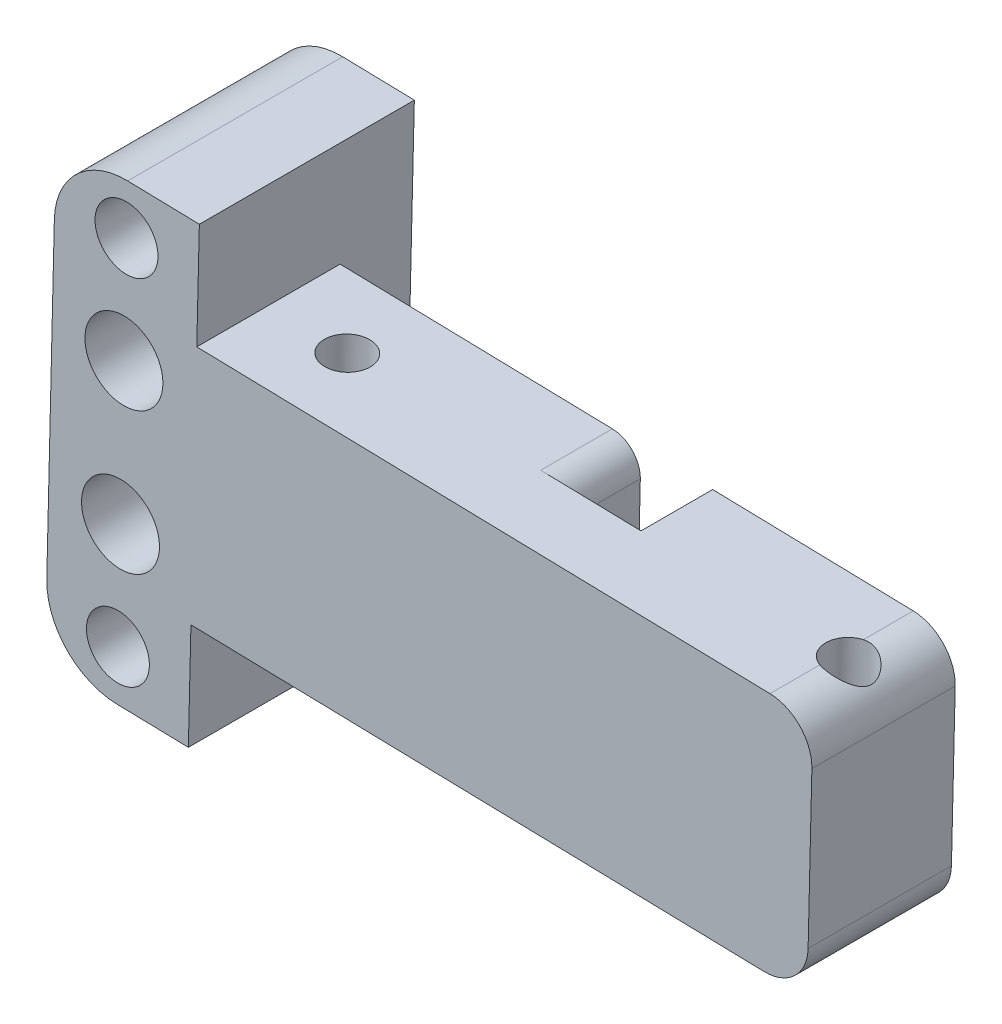
SolidWorks part; units mm, degrees
material "聚丁二烯(PB)"
ref_plane "前视基准面" through (0, 0, 0) normal (0, 0, 1) x (1, 0, 0)
ref_plane "上视基准面" through (0, 0, 0) normal (0, 1, 0) x (1, 0, 0)
ref_plane "右视基准面" through (0, 0, 0) normal (1, 0, 0) x (0, 0, -1)
other "Configuration Table"
sketch "草图1" plane through (0, 0, 0) normal (0, 0, 1) x (1, 0, 0)
  line L0 (24.1852, -7.0163) -> (24.4965, 5.98)
  line L1 (22.545, 8.0273) -> (-13.4447, 8.8895)
  line L2 (-13.4447, 8.8895) -> (-13.2651, 16.3873)
  line L3 (-13.2651, 16.3873) -> (-18.2636, 16.5071)
  line L4 (-23.3819, 11.6283) -> (-23.9088, -10.3654)
  line L5 (-19.03, -15.4837) -> (-14.0315, -15.6035)
  line L6 (-14.0315, -15.6035) -> (-13.8518, -8.1056)
  line L7 (-13.8518, -8.1056) -> (22.1378, -8.9678)
  arc A0 (24.4965, 5.98) -> (22.545, 8.0273) centre (22.4971, 6.0279) ccw
  arc A1 (-18.2636, 16.5071) -> (-23.3819, 11.6283) centre (-18.3834, 11.5085) ccw
  arc A2 (-23.9088, -10.3654) -> (-19.03, -15.4837) centre (-18.9103, -10.4852) ccw
  arc A3 (22.1378, -8.9678) -> (24.1852, -7.0163) centre (22.1857, -6.9684) ccw
  arc A4 (-16.7504, -12.0373) -> (-21.142, -11.9321) centre (-18.9462, -11.9847) ccw
  arc A5 (-21.142, -11.9321) -> (-16.7504, -12.0373) centre (-18.9462, -11.9847) ccw
  arc A6 (-16.0473, -4.552) -> (-21.4859, -4.4217) centre (-18.7666, -4.4869) ccw
  arc A7 (-21.4859, -4.4217) -> (-16.0473, -4.552) centre (-18.7666, -4.4869) ccw
  arc A8 (-15.8078, 5.4451) -> (-21.2464, 5.5754) centre (-18.5271, 5.5103) ccw
  arc A9 (-21.2464, 5.5754) -> (-15.8078, 5.4451) centre (-18.5271, 5.5103) ccw
  arc A10 (-16.1517, 12.9555) -> (-20.5432, 13.0607) centre (-18.3475, 13.0081) ccw
  arc A11 (-20.5432, 13.0607) -> (-16.1517, 12.9555) centre (-18.3475, 13.0081) ccw
extrude "凸台-拉伸1" add sketch "草图1" against normal blind 15
sketch "草图2" plane through (0, 0, -15) normal (0, 0, -1) x (-1, 0, 0)
  line L0 (13.4447, 8.8895) -> (13.8518, -8.1056)
  line L1 (13.8518, -8.1056) -> (-33.4158, -15.1213)
  line L2 (-33.4158, -15.1213) -> (-27.3795, 15.7432)
  line L3 (-27.3795, 15.7432) -> (13.4447, 8.8895)
extrude "切除-拉伸1" cut sketch "草图2" against normal blind 5
sketch "草图3" plane through (0.2051, 8.5625, 0) normal (0.024, 0.9997, 0) x (0.9997, -0.024, 0)
  line L0 (22.3463, 10) -> (-13.6537, 10) construction
  line L1 (12.3463, 10) -> (7.3463, 10)
  line L2 (12.3463, 10) -> (12.3463, 5)
  line L3 (12.3463, 5) -> (7.3463, 5)
  line L4 (7.3463, 10) -> (7.3463, 5)
  line L6 (24.3463, 10) -> (24.3463, 0) construction
  line L7 (22.3463, 0) -> (-13.6537, 0) construction
  circle A0 centre (21.8463, 5) radius 1.6
  circle A1 centre (-8.1537, 5) radius 1.6
  dimension "D3" = 2.5
  dimension "D4" = 3.2
  dimension "D1" = 5
  dimension "D2" = 12
  dimension "D6" = 5
  dimension "D5" = 2
extrude "切除-拉伸2" cut sketch "草图3" against normal blind 22
fillet "圆角1" radius 2 2 edges at (7.1421, -8.6086, -7.5) (7.5493, 8.3865, -7.5)
sketch "草图4" plane through (-0.202, -8.4326, 0) normal (-0.024, -0.9997, 0) x (0.9997, -0.024, 0)
  line L0 (-13.6537, 0) -> (22.3463, 0) construction
  line L1 (19.765, 0) -> (29.3463, 0)
  line L2 (19.765, 0) -> (19.765, -10)
  line L3 (19.765, -10) -> (29.3463, -10)
  line L4 (29.3463, 0) -> (29.3463, -10)
  line L5 (12.3463, -10) -> (22.3463, -10) construction
  line L6 (24.3463, -10) -> (24.3463, 0) construction
  dimension "D1" = 5
extrude "凸台-拉伸2" add sketch "草图4" against normal up to surface (17 mm away) up to face at (-9.5458, 8.7961, -5)
sketch "草图5" plane through (-0.202, -8.4326, 0) normal (-0.024, -0.9997, 0) x (0.9997, -0.024, 0)
  circle A0 centre (-8.1537, -5) radius 1.6 construction
  circle A1 centre (-8.1537, -5) radius 1.6
  circle A2 centre (26.8463, -5) radius 1.6
  dimension "D2" = 35
  dimension "D1" = 2
extrude "切除-拉伸3" cut sketch "草图5" against normal blind 18 contours A2 region at (26.6365, -9.0756, -5)
fillet "圆角2" radius 3 2 edges at (29.543, 7.8596, -5) (29.1358, -9.1355, -5)
